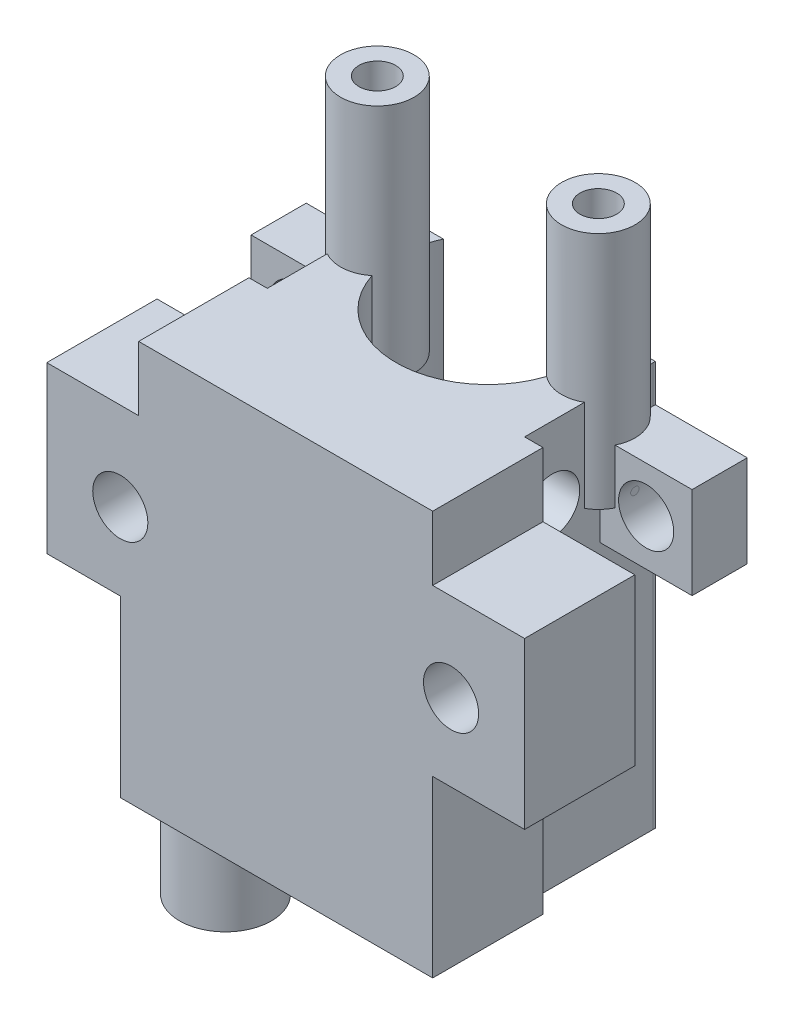
SolidWorks part; units mm, degrees
ref_plane "Plano frontal" through (0, 0, 0) normal (0, 0, 1) x (1, 0, 0)
ref_plane "Plano superior" through (0, 0, 0) normal (0, 1, 0) x (1, 0, 0)
ref_plane "Plano direito" through (0, 0, 0) normal (1, 0, 0) x (0, 0, -1)
sketch "Esboço1" plane through (0, 0, 0) normal (0, 0, 1) x (1, 0, 0)
  line L0 (-11.6371, -1.8328) -> (5.3629, -1.8328)
  line L6 (5.3629, -1.8328) -> (5.3629, 7.6672)
  line L7 (-10.6371, 20.1672) -> (5.3629, 20.1672)
  line L8 (-11.6371, 7.6672) -> (-11.6371, -1.8328)
  line L9 (5.3629, 16.6672) -> (10.3629, 16.6672)
  line L10 (10.3629, 16.6672) -> (10.3629, 7.6672)
  line L11 (10.3629, 7.6672) -> (5.3629, 7.6672)
  line L12 (-10.6371, 16.6672) -> (-15.6371, 16.6672)
  line L13 (-15.6371, 16.6672) -> (-15.6371, 7.6672)
  line L14 (-15.6371, 7.6672) -> (-11.6371, 7.6672)
  line L15 (-10.6371, 16.6672) -> (-10.6371, 20.1672)
  line L16 (5.3629, 16.6672) -> (5.3629, 20.1672)
  circle A2 centre (6.3629, 11.8672) radius 1.5
  circle A3 centre (-11.6371, 11.8672) radius 1.5
  dimension "D9" = 5
  dimension "D18" = 3
  dimension "D19" = 3
  dimension "D8" = 16
  dimension "D11" = 9
  dimension "D14" = 3.5
  dimension "D15" = 3.5
  dimension "D16" = 5
  dimension "D17" = 9
  dimension "D20" = 4
  dimension "D21" = 4
  dimension "D22" = 4.2
  dimension "D23" = 4.2
extrude "Ressalto-extrusão1" add sketch "Esboço1" along normal blind 6
sketch "Esboço6" plane through (0, 0, 0) normal (0, 0, -1) x (-1, 0, 0)
  line L0 (-5.3629, 20.1672) -> (10.6371, 20.1672) construction
  line L1 (-4.3629, 20.1672) -> (9.6371, 20.1672)
  line L2 (-4.3629, 20.1672) -> (-4.3629, -1.8328)
  line L3 (-4.3629, -1.8328) -> (9.6371, -1.8328)
  line L4 (9.6371, 20.1672) -> (9.6371, -1.8328)
  line L5 (11.6371, -1.8328) -> (-5.3629, -1.8328) construction
  line L6 (10.6371, 20.1672) -> (10.6371, 7.1672) construction
  line L7 (-5.3629, -1.8328) -> (-5.3629, 7.6672) construction
  dimension "D1" = 1
  dimension "D2" = 1
extrude "Ressalto-extrusão3" add sketch "Esboço6" along normal blind 12
sketch "Esboço7" plane through (0, -1.8328, 0) normal (0, -1, 0) x (1, 0, 0)
  line L0 (4.3629, 0) -> (-9.6371, 0)
  line L1 (-2.6371, 0) -> (-2.6371, -5)
  circle A0 centre (-2.6371, -5) radius 5
  dimension "D1" = 5
extrude "Corte-extrusão4" cut sketch "Esboço7" against normal through all
fillet "Filete3" radius 5 2 edges at (-9.6371, 9.1672, -12) (4.3629, 9.1672, -12)
sketch "Esboço8" plane through (0, -1.8328, 0) normal (0, -1, 0) x (-1, 0, 0)
  line L0 (2.6371, 5) -> (2.6371, -2.7)
  line L1 (2.6371, -2.7) -> (-3.9389, -2.7)
  line L2 (2.6371, -2.7) -> (9.2131, -2.7)
  dimension "D1" = 7.7
  dimension "D2" = 6.576
  dimension "D3" = 10.1259
  dimension "D4" = 6.576
sketch "Esboço15" plane through (0, 20.1672, 0) normal (0, 1, 0) x (1, 0, 0)
  line L0 (-7.6638, 5) -> (-9.6371, 5)
  line L1 (-9.6371, 7) -> (-9.6371, 0) construction
  line L2 (2.3895, 5) -> (4.3629, 5)
  line L3 (4.3629, 7) -> (4.3629, 0) construction
  circle A2 centre (-8.6505, 5) radius 2
  circle A3 centre (3.3762, 5) radius 2
  dimension "D1" = 4
  dimension "D2" = 4
extrude "Ressalto-extrusão13" add sketch "Esboço15" along normal blind 8 and the other way blind 5
sketch "Esboço17" plane through (0, 28.1672, 0) normal (0, 1, 0) x (1, 0, 0)
  circle A0 centre (-8.6505, 5) radius 1
  circle A1 centre (3.3762, 5) radius 1
  dimension "D1" = 2
  dimension "D2" = 2
extrude "Corte-extrusão6" cut sketch "Esboço17" against normal blind 8 contours A0 | A1
sketch3d "3DSketch4"
  line L0 (-9.6371, -1.8328, 0) -> (-9.6371, 20.1672, 0) construction
  point P0 (-9.6371, 8.771, 0)
ref_plane "Plano4" through (0, 0, -7.1152) normal (0, 0, -1) x (1, 0, 0)
sketch "Esboço21" plane through (0, 0, -7.1152) normal (0, 0, -1) x (1, 0, 0)
  line L1 (8.5566, 5.7142) -> (-14.1129, 5.7142)
  line L2 (8.5566, 5.7142) -> (8.5566, -25.4431)
  line L3 (8.5566, -25.4431) -> (-14.1129, -25.4431)
  line L4 (-14.1129, 5.7142) -> (-14.1129, -25.4431)
extrude "Corte-extrusão8" cut sketch "Esboço21" along normal blind 6
sketch "Esboço22" plane through (0, 0, -7.1152) normal (0, 0, -1) x (1, 0, 0)
  line L0 (-9.6358, 1.8328) -> (-9.6358, -20.1672) construction
  line L1 (-9.6358, -18.1259) -> (-14.6358, -18.1259)
  line L2 (-9.6358, -18.1259) -> (-9.6358, -13.1259)
  line L3 (-9.6358, -13.1259) -> (-14.6358, -13.1259)
  line L4 (-14.6358, -18.1259) -> (-14.6358, -13.1259)
  line L5 (-9.6358, -13.1259) -> (4.3629, -13.1259)
  line L6 (4.3629, -20.1672) -> (4.3629, -15.1672) construction
  line L8 (4.3629, -13.1259) -> (9.3629, -13.1259)
  line L9 (4.3629, -13.1259) -> (4.3629, -18.1259)
  line L10 (4.3629, -18.1259) -> (9.3629, -18.1259)
  line L11 (9.3629, -13.1259) -> (9.3629, -18.1259)
  circle A1 centre (-12.1358, -15.6259) radius 1.5
  circle A2 centre (6.8629, -15.6259) radius 1.5
  dimension "D3" = 3
  dimension "D6" = 3
  dimension "D1" = 5
  dimension "D2" = 5
  dimension "D4" = 5
  dimension "D5" = 5
extrude "Ressalto-extrusão15" add sketch "Esboço22" against normal blind 3 contours L4 L1 L2 L3 A1 | L11 L8 L9 L10 A2
sketch "Esboço23" plane through (0, -1.8328, 0) normal (0, -1, 0) x (1, 0, 0)
  circle A0 centre (-9.2131, 2.7) radius 2.5
  dimension "D1" = 5
extrude "Ressalto-extrusão16" add sketch "Esboço23" along normal blind 5
sketch "Esboço24" plane through (0, -6.8328, 0) normal (0, -1, 0) x (1, 0, 0)
  circle A0 centre (-9.2131, 2.7) radius 0.75
  dimension "D1" = 1.5
extrude "Corte-extrusão9" cut sketch "Esboço24" against normal blind 5
chamfer "Chanfro5" distance 1 angle 45 2 edges at (7.8629, 11.8672, 0) (-10.1371, 11.8672, 0)
sketch "Esboço25" plane through (-9.6371, 0, 0) normal (-1, 0, 0) x (0, 0, 1)
  line L0 (6, 16.6672) -> (6, 7.6672) construction
  line L1 (-3.2603, 20.1672) -> (0, 20.1672) construction
  circle A0 centre (-1.5, 16.1672) radius 1.5
  dimension "D2" = 4
  dimension "D3" = 3
  dimension "D1" = 7.5
extrude "Corte-extrusão11" cut sketch "Esboço25" against normal blind 14
